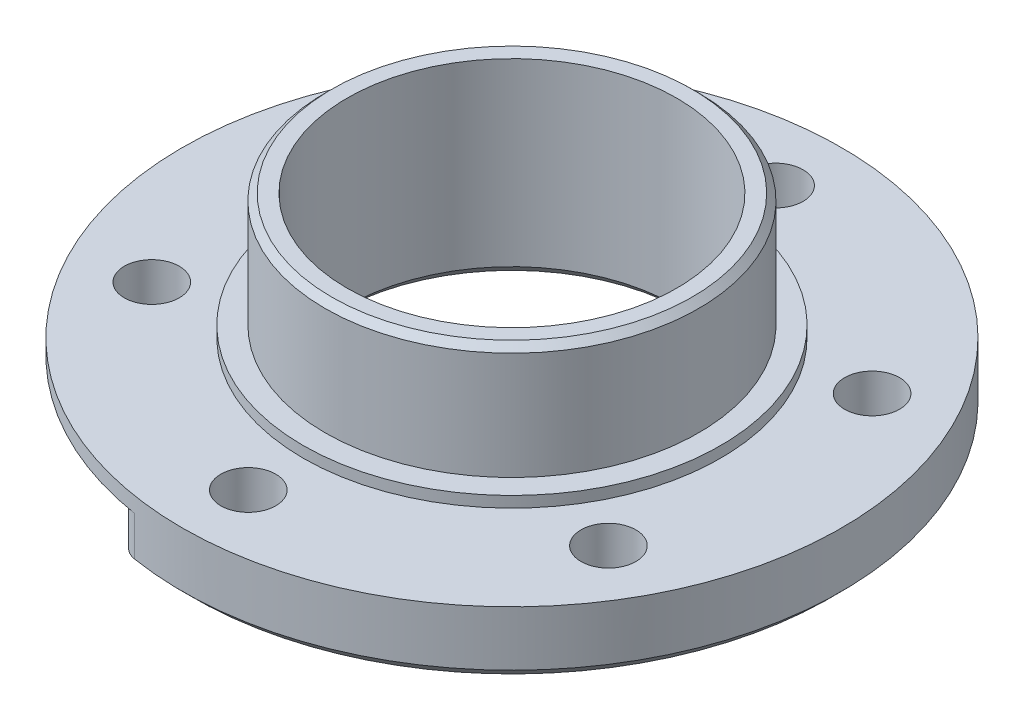
SolidWorks part; units mm, degrees
material "3.3523 (EN-AW 5052)"
ref_plane "前视基准面" through (0, 0, 0) normal (0, 0, 1) x (1, 0, 0)
ref_plane "上视基准面" through (0, 0, 0) normal (0, 1, 0) x (1, 0, 0)
ref_plane "右视基准面" through (0, 0, 0) normal (1, 0, 0) x (0, 0, -1)
other "Configuration Table"
sketch "草图1" plane through (0, 0, 0) normal (0, 1, 0) x (1, 0, 0)
  circle A0 centre (0, 0) radius 15
  circle A1 centre (0, 0) radius 7.5
  circle A2 centre (0, 0) radius 12 construction
  circle A3 centre (0, 12) radius 1
  circle A4 centre (10.3923, 6) radius 1
  circle A5 centre (10.3923, -6) radius 1
  circle A6 centre (0, -12) radius 1
  circle A7 centre (-10.3923, -6) radius 1
  circle A8 centre (-10.3923, 6) radius 1
  point P20 (0, 0)
  dimension "D1" = 30
  dimension "D2" = 15
  dimension "D3" = 24
  dimension "D4" = 2
  dimension "D5" = 6
extrude "凸台-拉伸1" add sketch "草图1" along normal blind 3
sketch "草图2" plane through (0, 3, 0) normal (0, 1, 0) x (1, 0, 0)
  circle A1 centre (0, 0) radius 7.5
  circle A2 centre (0, 0) radius 8.5
  circle A3 centre (0, 0) radius 7.5 construction
  dimension "D1" = 17
extrude "凸台-拉伸2" add sketch "草图2" along normal blind 5.7
sketch "草图3" plane through (0, 3, 0) normal (0, 1, 0) x (1, 0, 0)
  circle A0 centre (0, 0) radius 8.5
  circle A1 centre (0, 0) radius 8.5 construction
  circle A2 centre (0, 0) radius 9.5
  dimension "D1" = 1
extrude "凸台-拉伸3" add sketch "草图3" along normal blind 0.5
sketch "草图4" plane through (0, 0, 0) normal (0, -1, 0) x (1, 0, 0)
  line L0 (0, 0) -> (-15, 0) construction
  line L2 (-24.257, 1.5) -> (-10, 1.5)
  line L3 (-24.257, 1.5) -> (-24.257, -1.5)
  line L4 (-24.257, -1.5) -> (-10, -1.5)
  line L5 (-10, 1.5) -> (-10, -1.5)
  circle A0 centre (0, 0) radius 15 construction
  dimension "D1" = 10
  dimension "D2" = 1.5
hole_wizard "M3 螺纹孔1" positions "草图5" profile "草图6" tap size "M3" standard "GB" end condition through all
sketch "草图5" plane through (0, 0, 0) normal (0, -1, 0) x (-1, 0, 0)
  point P0 (0, 12)
  point P3 (10.3923, 6)
  point P6 (10.3923, -6)
  point P9 (0, -12)
  point P12 (-10.3923, -6)
  point P15 (-10.3923, 6)
sketch "草图6" plane through (0, 0, -12) normal (1, 0, 0) x (0, 0, -1)
  line L0 (0, 0) -> (0, 8.7)
  line L1 (0, 8.7) -> (1.25, 8.7)
  line L2 (1.25, 8.7) -> (1.25, 0)
  line L5 (1.25, 0) -> (0, 0)
  line L11 (0, -6.35) -> (0, 107.95) construction
  dimension "通孔螺纹孔钻头直径" = 2.5
  dimension "通孔螺纹孔钻头深度" = 8.7
chamfer "倒角2" distance 0.3 angle 45 1 edges at (0, 8.7, 8.5)
sketch "草图7" plane through (0, 0, 0) normal (0, -1, 0) x (1, 0, 0)
  line L0 (0, 0) -> (-9, 15.5885) construction
  line L1 (-3.4641, -2) -> (-12.4641, 13.5885)
  line L2 (3.4641, 2) -> (-5.5359, 17.5885)
  line L3 (0, 0) -> (-15.1433, 0) construction
  arc A0 (-3.4641, -2) -> (3.4641, 2) centre (0, 0) ccw
  arc A1 (-5.5359, 17.5885) -> (-12.4641, 13.5885) centre (-9, 15.5885) ccw
  point P3 (-4.5, 7.7942)
  dimension "D1" = 8
  dimension "D2" = 60
  dimension "D3" = 18
extrude "切除-拉伸2" cut sketch "草图7" against normal blind 2.3
fillet "圆角2" radius 1 5 edges at (-3.75, 2.3, 6.4952) (0.292, 1.15, 7.4943) (-6.6362, 1.15, 3.4943) (-3.7643, 1.15, 14.52) (-10.6925, 1.15, 10.52)
chamfer "倒角3" distance 0.5 angle 45 8 edges at (3.75, 0, -6.4952) (0.3483, 0, 7.6144) (-6.7684, 0, 3.5056) (-1.5235, 0, 10.6388) (-8.4517, 0, 6.6388) (-3.1111, 0, 14.2547) (-10.7894, 0, 9.8216) (7.5, 0, -12.9904)
